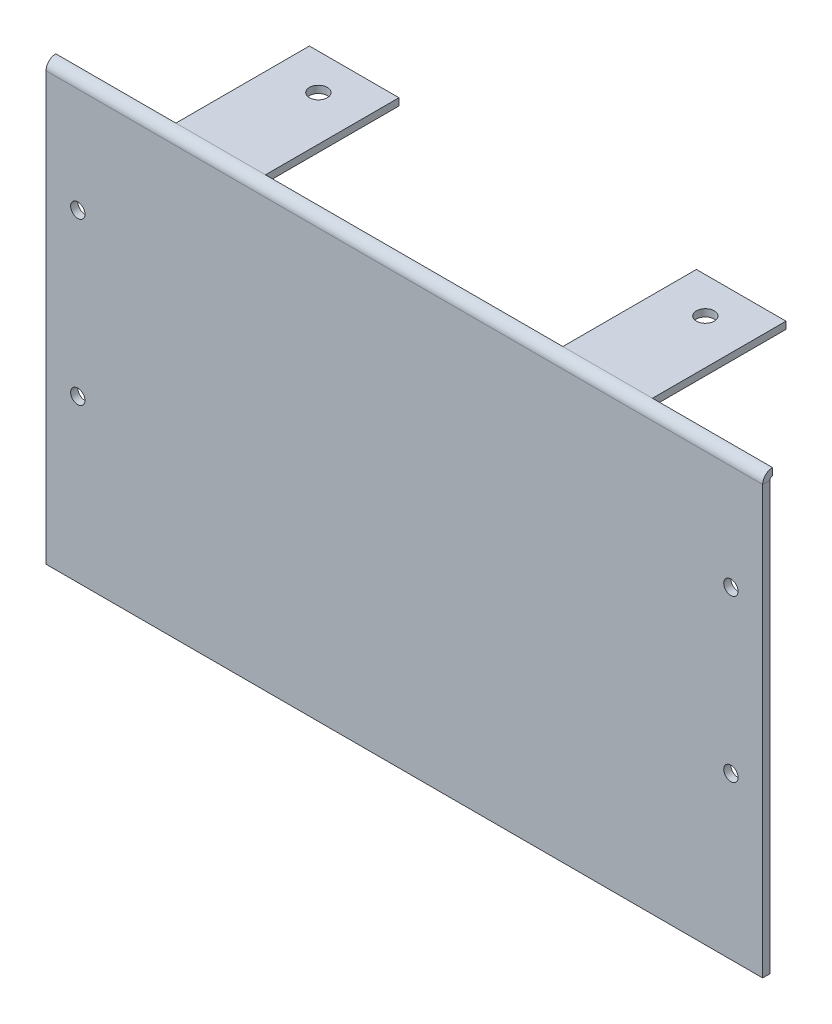
SolidWorks part; units mm, degrees
note: The reader was unsure of these and kept them because the rebuilt part matched: flange length of "Edge-Flange1".
ref_plane "Front Plane" through (0, 0, 0) normal (0, 0, 1) x (1, 0, 0)
ref_plane "Top Plane" through (0, 0, 0) normal (0, 1, 0) x (1, 0, 0)
ref_plane "Right Plane" through (0, 0, 0) normal (1, 0, 0) x (0, 0, -1)
sketch "Sketch2" plane through (0, 0, 0) normal (0, 0, 1) x (1, 0, 0)
  line L1 (0, 0) -> (200, 0)
  line L2 (0, 0) -> (0, 120)
  line L3 (0, 120) -> (200, 120)
  line L4 (200, 0) -> (200, 120)
  dimension "D1" = 120
  dimension "D2" = 200
base flange "Base-Flange1" sketch "Sketch2" thickness 2 reverse thickness direction no parameters "D1"=0.7366
sketch "Sketch7" plane through (0, 0, 0) normal (0, 0, 1) x (1, 0, 0)
  line L0 (200, 120) -> (0, 120) construction
  line L1 (0, 120) -> (0, 0) construction
  line L2 (200, 0) -> (200, 120) construction
  circle A0 centre (8.87, 90) radius 2
  circle A1 centre (8.87, 45) radius 2
  circle A2 centre (191.13, 45) radius 2
  circle A3 centre (191.13, 90) radius 2
  dimension "D1" = 4
  dimension "D2" = 30
  dimension "D3" = 8.87
  dimension "D4" = 45
  dimension "D5" = 8.87
extrude "Cut-Extrude1" cut sketch "Sketch7" against normal up to next normal cut yes
edge flange "Edge-Flange1" sketch "Sketch10" flange angle 90 flange length 40 flange position material outside bend radius 0.7366 thickness 2 relief rectangular parameters "D6"=10
sketch "Sketch10" plane through (0, 120, -2) normal (0, -1, 0) x (-1, 0, 0)
  line L2 (-200, 0) -> (-200, 38)
  line L3 (-200, 38) -> (0, 38)
  line L4 (0, 38) -> (0, 0)
  line L6 (0, 0) -> (-200, 0) construction
  line L7 (0, 0) -> (-200, 0)
bend "EdgeBend1" bend radius 0.7366 bend angle 90 parameters "D5"=1
sketch "Sketch11" plane through (0, 122, 0) normal (0, 1, 0) x (1, 0, 0)
  line L0 (200, 30) -> (154, 30) construction
  line L2 (46, 30) -> (0, 30) construction
  line L4 (200, 40) -> (200, 2.7366) construction
  line L5 (0, 2.7366) -> (0, 40) construction
  line L6 (0, 40) -> (200, 40) construction
  line L7 (0, 2.7366) -> (200, 2.7366) construction
  line L8 (200, 2.7366) -> (166.5, 2.7366)
  line L9 (200, 2.7366) -> (200, 40)
  line L10 (200, 40) -> (166.5, 40)
  line L11 (166.5, 2.7366) -> (166.5, 40)
  line L12 (141.5, 2.7366) -> (58.5, 2.7366)
  line L13 (141.5, 2.7366) -> (141.5, 40)
  line L14 (141.5, 40) -> (58.5, 40)
  line L15 (58.5, 2.7366) -> (58.5, 40)
  line L16 (154, 40) -> (154, 2.7366) construction
  line L17 (33.5, 2.7366) -> (0, 2.7366)
  line L18 (33.5, 2.7366) -> (33.5, 40)
  line L19 (33.5, 40) -> (0, 40)
  line L20 (0, 2.7366) -> (0, 40)
  line L21 (46, 2.7366) -> (46, 40) construction
  circle A0 centre (154, 30) radius 2.5
  circle A1 centre (46, 30) radius 2.5
  dimension "D1" = 5
  dimension "D2" = 108
  dimension "D3" = 10
  dimension "D4" = 25
  dimension "D5" = 25
extrude "Cut-Extrude2" cut sketch "Sketch11" against normal up to next normal cut yes
sketch "Bend-Lines1" plane through (0, 0, 0) normal (0, 1, 0) x (1, 0, 0)
sketch "Bounding-Box1" plane through (0, 0, 0) normal (0, 1, 0) x (1, 0, 0)
sheet metal parameters "Sheet-Metal1" thickness 2 parameters "D1"=0.7366
flat pattern "Flat-Pattern1" [suppressed]
sketch "Bend-Lines2" plane through (0, 0, 0) normal (0, 1, 0) x (1, 0, 0)
sketch "Bounding-Box2" [suppressed] plane through (0, 0, 0) normal (0, 1, 0) x (1, 0, 0)
sheet metal parameters "Sheet-Metal2" thickness 2 parameters "D1"=0.7366
flat pattern "Flat-Pattern1"
sketch "Bend-Lines2" plane through (0, 0, 0) normal (0, 1, 0) x (1, 0, 0)
sketch "Bounding-Box2" [suppressed] plane through (0, 0, 0) normal (0, 1, 0) x (1, 0, 0)
sheet metal parameters "Sheet-Metal3" thickness 2 parameters "D1"=0.7366
flat pattern "Flat-Pattern1" [suppressed]
sketch "Bend-Lines2" plane through (0, 0, 0) normal (0, 1, 0) x (1, 0, 0)
sketch "Bounding-Box2" [suppressed] plane through (0, 0, 0) normal (0, 1, 0) x (1, 0, 0)
bend of the flat pattern "Flatten-<EdgeBend1>1"
sheet metal parameters "Sheet-Metal4" thickness 2 parameters "D1"=0.7366
flat pattern "Flat-Pattern1" [suppressed]
sketch "Bend-Lines2" plane through (0, 0, 0) normal (0, 1, 0) x (1, 0, 0)
sketch "Bounding-Box2" [suppressed] plane through (0, 0, 0) normal (0, 1, 0) x (1, 0, 0)
bend of the flat pattern "Flatten-<EdgeBend1>1"
